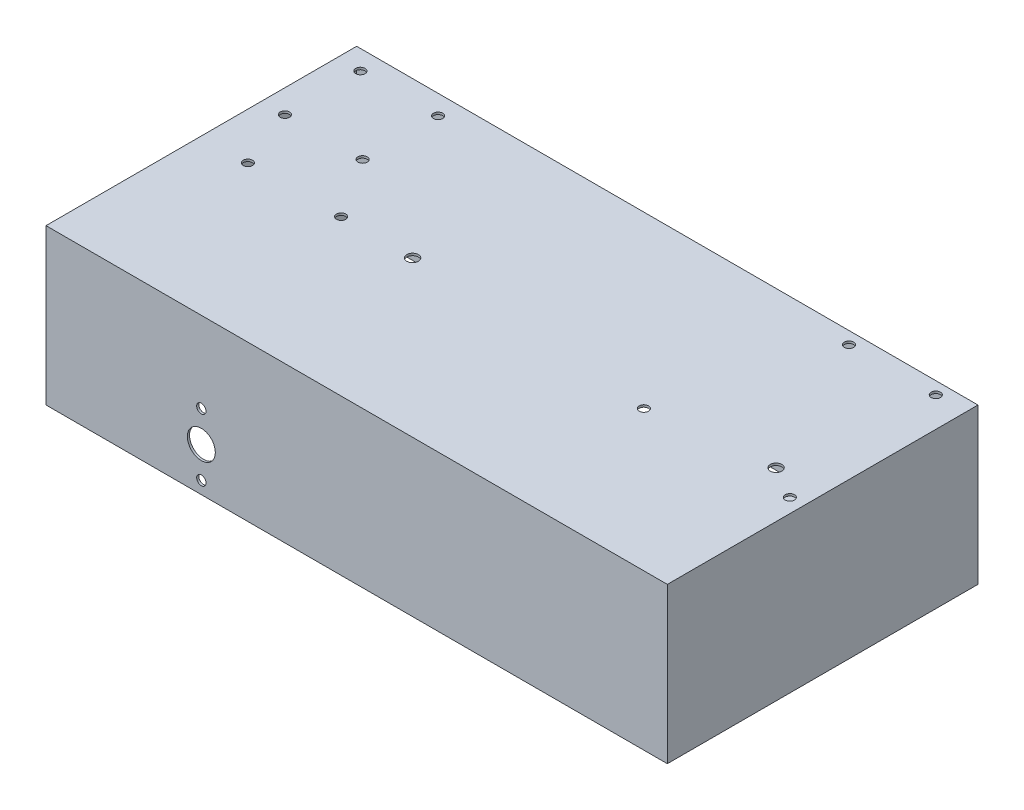
SolidWorks part; units mm, degrees
ref_plane "Front Plane" through (0, 0, 0) normal (0, 0, 1) x (1, 0, 0)
ref_plane "Top Plane" through (0, 0, 0) normal (0, 1, 0) x (1, 0, 0)
ref_plane "Right Plane" through (0, 0, 0) normal (1, 0, 0) x (0, 0, -1)
sketch "Sketch1" plane through (0, 0, 0) normal (0, 1, 0) x (1, 0, 0)
  line L1 (0, 50) -> (200, 50)
  line L2 (0, 50) -> (0, -50)
  line L3 (0, -50) -> (200, -50)
  line L4 (200, 50) -> (200, -50)
  point P4 (0, 0)
  dimension "D1" = 200
  dimension "D2" = 100
extrude "Boss-Extrude1" add sketch "Sketch1" along normal blind 50
sketch "Sketch2" plane through (0, 0, 50) normal (0, 0, 1) x (1, 0, 0)
  line L0 (0, 50) -> (0, 0) construction
  line L1 (50, 24) -> (50, 4) construction
  line L2 (0, 50) -> (200, 50) construction
  circle A0 centre (50, 14) radius 4.5
  circle A1 centre (50, 4) radius 1.5
  circle A2 centre (50, 24) radius 1.5
  point P0 (50, 14)
  point P9 (50, 14)
  dimension "D3" = 9
  dimension "D4" = 3
  dimension "D1" = 50
  dimension "D2" = 36
  dimension "D5" = 20
sketch "Sketch3" plane through (0, 0, 0) normal (0, -1, 0) x (1, 0, 0)
  line L0 (0.7, 49.3) -> (0.7, -49.3)
  line L1 (0.7, -49.3) -> (199.3, -49.3)
  line L2 (199.3, -49.3) -> (199.3, 49.3)
  line L3 (199.3, 49.3) -> (0.7, 49.3)
  line L4 (0, 50) -> (0, -50)
  line L5 (0, -50) -> (200, -50)
  line L6 (200, -50) -> (200, 50)
  line L7 (200, 50) -> (0, 50)
  line L8 (0, 50) -> (0, -50) construction
  line L9 (0, -50) -> (200, -50) construction
  line L10 (200, -50) -> (200, 50) construction
  line L11 (200, 50) -> (0, 50) construction
  dimension "D1" = 0
  dimension "D2" = 0.7
extrude "Cut-Extrude1" cut sketch "Sketch3" against normal offset from surface (49.3 mm away) 0.7 up to face at (100, 50, 0)
sketch "Sketch4" plane through (0, 0, 0) normal (0, -1, 0) x (1, 0, 0)
  line L0 (0.7, -49.3) -> (199.3, -49.3) construction
  line L1 (145, -49.3) -> (199.3, -49.3)
  line L2 (145, -49.3) -> (145, 49.3)
  line L3 (145, 49.3) -> (199.3, 49.3)
  line L4 (199.3, -49.3) -> (199.3, 49.3)
  line L5 (199.3, 49.3) -> (0.7, 49.3) construction
  line L6 (160, -47.9) -> (160, 49.3) construction
  line L7 (200, -50) -> (200, 50) construction
  line L8 (199.3, -49.3) -> (199.3, 49.3) construction
  circle A0 centre (160, 0.7) radius 11.43 construction
  point P12 (160, 0.7)
  dimension "D3" = 22.86
  dimension "D1" = 40
  dimension "D2" = 55
  dimension "D4" = 50
extrude "Boss-Extrude2" add sketch "Sketch4" against normal blind 0.7
extrude "Cut-Extrude2" cut sketch "Sketch2" against normal through all
sketch "Sketch8" plane through (0, 0, 0) normal (0, -1, 0) x (1, 0, 0)
  line L0 (160, -47.9) -> (160, 49.3) construction
  circle A0 centre (160, 8.45) radius 1.21
  circle A1 centre (160, -7.05) radius 1.21
  dimension "D2" = 2.42
  dimension "D1" = 7.75
  dimension "D3" = 7.75
extrude "Cut-Extrude6" cut sketch "Sketch8" against normal blind 1.8 contours A1 | A0
sketch "Sketch9" plane through (0, 50, 0) normal (0, 1, 0) x (1, 0, 0)
  line L0 (0, 0) -> (200, 0) construction
  line L1 (200, 50) -> (200, -50) construction
  line L2 (0, 50) -> (200, 50) construction
  line L5 (7.5, 43.7) -> (32.5, 43.7) construction
  line L6 (7.5, 43.7) -> (7.5, 19.4) construction
  line L7 (7.5, 19.4) -> (32.5, 19.4) construction
  line L8 (32.5, 43.7) -> (32.5, 19.4) construction
  line L9 (0, -50) -> (0, 50) construction
  circle A0 centre (15, 0) radius 1.5
  circle A1 centre (45, 0) radius 1.5
  circle A2 centre (7.5, 43.7) radius 1.5
  circle A3 centre (7.5, 19.4) radius 1.5
  circle A4 centre (32.5, 43.7) radius 1.5
  circle A5 centre (32.5, 19.4) radius 1.5
  dimension "D1" = 3
  dimension "D4" = 25
  dimension "D8" = 3
  dimension "D2" = 15
  dimension "D3" = 30
  dimension "D5" = 24.3
  dimension "D6" = 6.3
  dimension "D7" = 7.5
sketch "Sketch10" plane through (0, 49.3, 0) normal (0, -1, 0) x (1, 0, 0)
  line L0 (0, 0) -> (200, 0)
  line L1 (200, -50) -> (200, 50) construction
  circle A0 centre (185, 0) radius 1.87
  circle A1 centre (68, 0) radius 1.87
  dimension "D2" = 3.74
  dimension "D1" = 117
  dimension "D3" = 15
extrude "Cut-Extrude8" cut sketch "Sketch10" against normal up to surface (0.7 mm away) contours A0 | A1 up to face at (100, 50, 0)
extrude "Cut-Extrude7" cut sketch "Sketch9" against normal up to next
sketch "Sketch11" plane through (143.38, 50, -175.08) normal (0, 1, 0) x (0, 0, 1)
  line L6 (129.04, 19.06) -> (129.04, 47) construction
  circle A0 centre (129.04, 47) radius 1.5
  circle A1 centre (181.11, 52.08) radius 1.5
  circle A2 centre (179.84, 3.82) radius 1.5
  circle A3 centre (129.04, 19.06) radius 1.5
  point P12 (195.08, 54.62)
  dimension "D8" = 3
  dimension "D1" = 13.97
  dimension "D2" = 66.04
  dimension "D3" = 15.24
  dimension "D4" = 2.54
  dimension "D5" = 7.62
  dimension "D6" = 50.8
  dimension "D7" = 35.56
  dimension "D9" = 70
  dimension "D10" = 2
extrude "Cut-Extrude9" cut sketch "Sketch11" against normal up to surface (0.7 mm away) up to face at (7.5, 49.3, -17.9)
